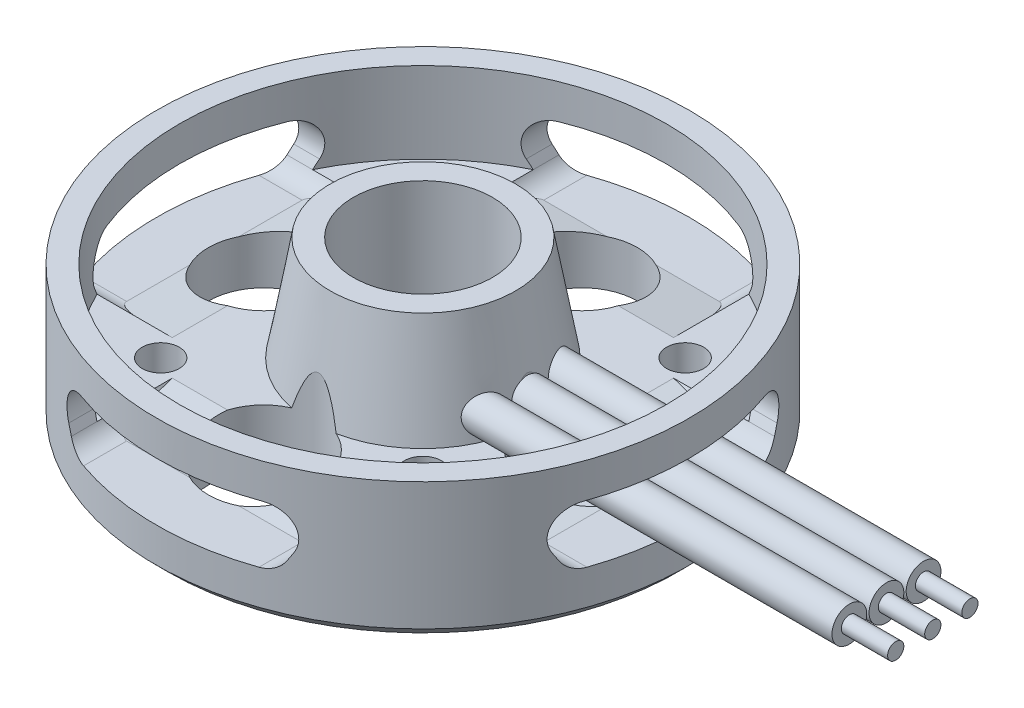
SolidWorks part; units mm, degrees
material "1060 Alloy"
ref_plane "Front Plane" through (0, 0, 0) normal (0, 0, 1) x (1, 0, 0)
ref_plane "Top Plane" through (0, 0, 0) normal (0, 1, 0) x (1, 0, 0)
ref_plane "Right Plane" through (0, 0, 0) normal (1, 0, 0) x (0, 0, -1)
sketch "Sketch1" plane through (0, 0, 0) normal (0, 0, 1) x (1, 0, 0)
  line L0 (0, 0) -> (0, 15.561) construction
  line L1 (0, 0) -> (11.5, 0)
  line L2 (11.5, 0) -> (11.5, 6)
  line L3 (11.5, 6) -> (10.5, 6)
  line L4 (10.5, 6) -> (10.5, 2.5)
  line L5 (10.5, 2.5) -> (0, 2.5)
  line L6 (0, 0) -> (0, 2.5)
  dimension "D1" = 23
  dimension "D2" = 1
  dimension "D3" = 2.5
  dimension "D4" = 6
revolve "Revolve1" add sketch "Sketch1" angle 360 about L0
chamfer "Chamfer1" distance 0.5 angle 45 1 edges at (0, 0, -11.5)
ref_plane "Plane1" through (0, 0, 11.5) normal (0, 0, 1) x (1, 0, 0)
sketch "Sketch4" plane through (0, 0, 11.5) normal (0, 0, 1) x (1, 0, 0)
  line L0 (0, 0) -> (0, 6) construction
  line L1 (11.5, 6) -> (-11.5, 6) construction
  line L2 (11.5, 6) -> (-11.5, 6) construction
  line L3 (-3.9, 3.4) -> (3.9, 3.4) construction
  line L4 (-3.9, 4.5) -> (3.9, 4.5)
  line L5 (-3.9, 2.3) -> (3.9, 2.3)
  line L6 (-4.8526, 2.85) -> (-4.6506, 2.5)
  line L7 (-3.7845, 2) -> (3.7845, 2)
  line L8 (4.8526, 2.85) -> (4.6506, 2.5)
  arc A0 (-3.9, 4.5) -> (-3.9, 2.3) centre (-3.9, 3.4) ccw
  arc A1 (3.9, 2.3) -> (3.9, 4.5) centre (3.9, 3.4) ccw
  arc A2 (4.6506, 2.5) -> (3.7845, 2) centre (3.7845, 3) cw
  arc A3 (-4.6506, 2.5) -> (-3.7845, 2) centre (-3.7845, 3) ccw
  point P7 (0, 3.4)
  point P18 (4.3619, 2)
  point P21 (-4.3619, 2)
  dimension "D1" = 10
  dimension "D4" = 1
  dimension "D2" = 1.5
  dimension "D3" = 60
  dimension "D5" = 2.2
  dimension "D6" = 2
extrude "Cut-Extrude3" cut sketch "Sketch4" against normal blind 2.5 contours L5 A1 L4 A0 | L6 A3 L7 A2 L8 A1 L5 A0 region at (0, 3.4, 11.5) region at (0, 2.1656, 11.5)
chamfer "Chamfer4" distance 0.5 angle 80 1 edges at (0, 2.5, 9) first distance on face at (0, 2.192, 9)
pattern_circular "CirPattern1" count 4 over 360 about axis through (0, 0, 0) along (0, -1, 0) of "Cut-Extrude3", "Chamfer4"
sketch "Sketch5" plane through (0, 0, 0) normal (0, -1, 0) x (1, 0, 0)
  circle A0 centre (0, 0) radius 3
  dimension "D1" = 6
extrude "Cut-Extrude4" cut sketch "Sketch5" against normal blind 3
sketch "Sketch6" plane through (0, 0, 0) normal (1, 0, 0) x (0, 0, -1)
  line L0 (6.1644, 2.5) -> (3, 2.5)
  line L1 (-3, 2.5) -> (-6.1644, 2.5)
  line L2 (-3, 2.5) -> (-4.8, 2.5)
  line L3 (-3, 2.5) -> (-3, 7)
  line L4 (-3, 7) -> (-4, 7)
  line L5 (-4, 7) -> (-4.8, 2.5)
  line L6 (0, 0) -> (0, 6.6036) construction
  dimension "D1" = 4.5
  dimension "D2" = 1
  dimension "D3" = 1.8
revolve "Revolve2" add sketch "Sketch6" angle 360 about L6
sketch "Sketch7" plane through (0, 0, 0) normal (0, -1, 0) x (1, 0, 0)
  line L0 (0, 0) -> (-6.875, 0) construction
  line L1 (0, 0) -> (0, -5.0537) construction
  line L2 (-4.5, 0) -> (-4.5, -3.582) construction
  line L3 (-9.25, 0) -> (-9.25, -3.3701) construction
  circle A0 centre (-6.875, 0) radius 2.375
  dimension "D1" = 18.5
  dimension "D2" = 9
extrude "Cut-Extrude5" cut sketch "Sketch7" against normal blind 5
pattern_circular "CirPattern2" count 4 over 360 about axis through (0, 3, 0) along (0, -1, 0) of "Cut-Extrude5"
sketch "Sketch8" plane through (0, 0, 0) normal (0, 0, 1) x (1, 0, 0)
  line L0 (4.5, 0) -> (9.25, 0) construction
  line L1 (4.5, 0) -> (9.25, 0) construction
  line L2 (6.875, 0) -> (6.875, 1) construction
  line L3 (4.5, 4.1875) -> (4.5, 0)
  line L4 (9.25, 0) -> (9.25, 2)
  line L5 (9.25, 0) -> (9.25, 1.5)
  line L6 (4.5, 4.1875) -> (4.5, 0) construction
  line L7 (6.875, 1) -> (6.875, 1.5)
  line L8 (6.875, 1.5) -> (9.25, 1.5)
  arc A0 (9.25, 0) -> (6.875, 1) centre (6.875, -2.3203) ccw
  dimension "D1" = 1
  dimension "D2" = 1.5
revolve "Revolve3" add sketch "Sketch8" angle 360 about L2
sketch "Sketch9" plane through (0, 0, 0) normal (0, -1, 0) x (1, 0, 0)
  line L0 (0, 0) -> (4.2426, 4.2426) construction
  line L1 (0, 0) -> (5.6569, -5.6569) construction
  line L2 (0, 0) -> (3, 0) construction
  circle A0 centre (0, 0) radius 8 construction
  circle A1 centre (0, 0) radius 6 construction
  circle A2 centre (0, 0) radius 3 construction
  dimension "D1" = 16
  dimension "D2" = 12
  dimension "D3" = 45
  dimension "D4" = 45
hole_wizard "M2 Tapped Hole1" positions "3DSketch1" profile "Sketch10" tap size "M2" standard "ISO"
sketch3d "3DSketch1"
  point P0 (4.2426, 0, 4.2426)
  point P3 (5.6569, 0, -5.6569)
sketch "Sketch10" plane through (4.2426, 0, 4.2426) normal (1, 0, 0) x (0, 0, -1)
  line L0 (0, 0) -> (0, 5.6807)
  line L1 (0, 5.6807) -> (0.8, 5.2)
  line L2 (0.8, 5.2) -> (0.8, 0)
  line L5 (0.8, 0) -> (0, 0)
  line L10 (0, 5.6807) -> (-0.8, 5.2) construction
  line L11 (0, -6.35) -> (0, 107.95) construction
  dimension "Tap Drill Dia." = 1.6
  dimension "Tap Drill Depth" = 5.2
  dimension "Drill Angle" = 118
cosmetic thread "Hole Thread1" parameters "D1"=2.5, "D2"=2
cosmetic thread "Hole Thread2" parameters "D1"=2.5, "D2"=2
pattern_circular "CirPattern3" count 2 over 360 about axis through (0, 3, 0) along (0, -1, 0) of "M2 Tapped Hole1"
sketch "Sketch11" plane through (0, 0, 0) normal (1, 0, 0) x (0, 0, -1)
  line L1 (-4.0159, 2.6) -> (4.0159, 2.6) construction
  line L2 (0, 0) -> (0, 2.6) construction
  line L3 (0, 2.6) -> (0, 3.35) construction
  circle A0 centre (0, 3.35) radius 0.75
  circle A1 centre (1.6, 3.35) radius 0.75
  circle A2 centre (-1.6, 3.35) radius 0.75
  dimension "D1" = 1.5
  dimension "D3" = 1.6
  dimension "D2" = 1.6
  dimension "D4" = 2.6
extrude "Boss-Extrude2" add sketch "Sketch11" along normal blind 20 contours A2 | A1 | A0 region at (0, 3.35, 0) region at (0, 3.35, -1.6) region at (0, 3.35, 1.6)
sketch "Sketch13" plane through (0, 7, 0) normal (0, 1, 0) x (1, 0, 0)
  circle A0 centre (0, 0) radius 3 construction
  circle A1 centre (0, 0) radius 3
extrude "Cut-Extrude6" cut sketch "Sketch13" against normal blind 6
sketch "Sketch14" plane through (20, 0, 0) normal (1, 0, 0) x (0, 0, -1)
  circle A3 centre (-1.6, 3.35) radius 0.35
  circle A4 centre (-1.6, 3.35) radius 0.35
  circle A6 centre (0, 3.35) radius 0.35
  circle A7 centre (0, 3.35) radius 0.35
  circle A10 centre (1.6, 3.35) radius 0.35
  circle A11 centre (1.6, 3.35) radius 0.35
  dimension "D1" = 0.4
  dimension "D2" = 0.4
  dimension "D3" = 0.4
extrude "Boss-Extrude3" add sketch "Sketch14" along normal blind 2 separate body
